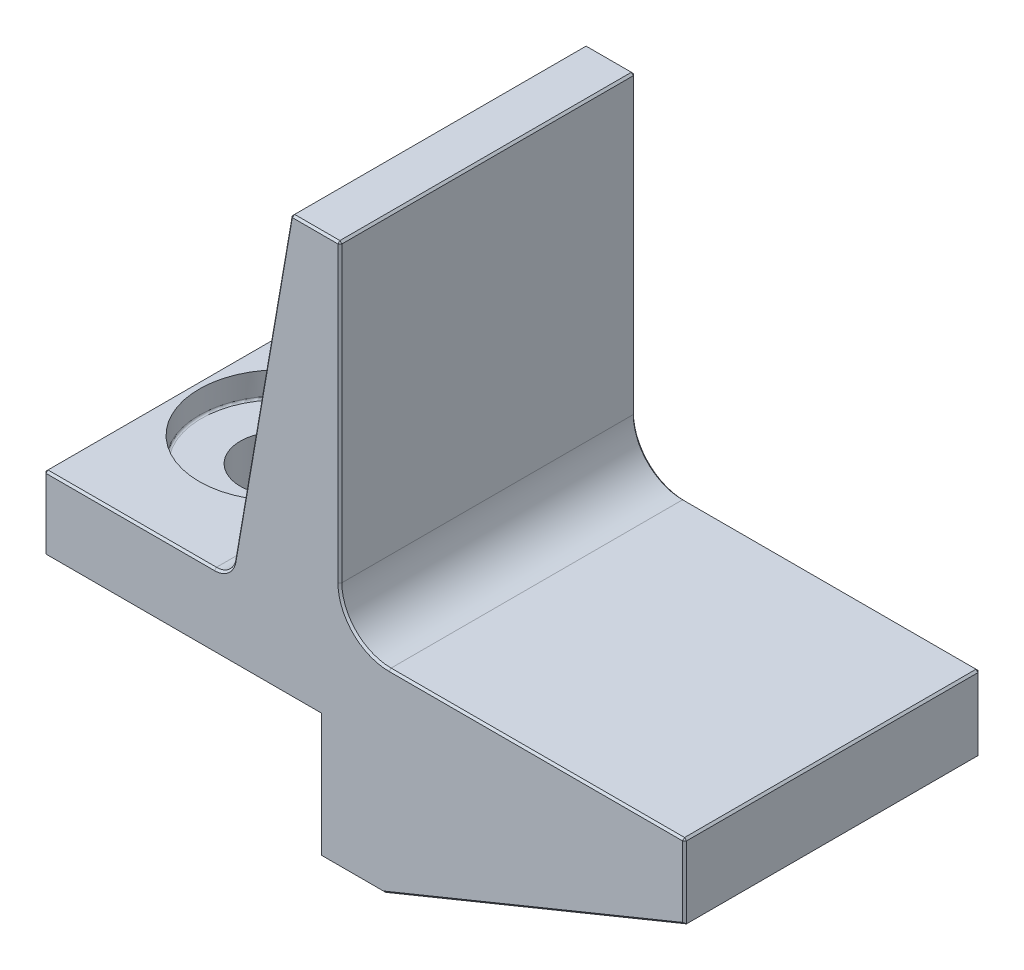
SolidWorks part; units mm, degrees
material "7075-T6 (SN)"
ref_plane "Front Plane" through (0, 0, 0) normal (0, 0, 1) x (1, 0, 0)
ref_plane "Top Plane" through (0, 0, 0) normal (0, 1, 0) x (1, 0, 0)
ref_plane "Right Plane" through (0, 0, 0) normal (1, 0, 0) x (0, 0, -1)
sketch "Sketch1" plane through (0, 0, 0) normal (0, 0, 1) x (1, 0, 0)
  line L0 (0, 0) -> (44.45, 0)
  line L1 (44.45, 0) -> (44.45, -9.525)
  line L2 (-2.6008, -9.525) -> (-38.1608, -9.525)
  line L3 (-38.1608, -9.525) -> (-38.1608, 0)
  line L4 (-38.1608, 0) -> (-14.0308, 0)
  line L5 (-14.0308, 0) -> (-6.35, 44.45)
  line L6 (-6.35, 44.45) -> (0, 44.45)
  line L7 (0, 44.45) -> (0, 0)
  line L8 (-2.6008, -9.525) -> (-2.6008, -25.4)
  line L9 (-2.6008, -25.4) -> (5.6542, -25.4)
  line L10 (5.6542, -25.4) -> (44.45, -9.525)
  dimension "D1" = 44.45
  dimension "D2" = 44.45
  dimension "D3" = 9.525
  dimension "D4" = 38.1608
  dimension "D5" = 6.35
  dimension "D6" = 24.13
  dimension "D7" = 35.56
  dimension "D8" = 9.525
  dimension "D9" = 15.875
  dimension "D10" = 8.255
extrude "Boss-Extrude1" add sketch "Sketch1" along normal blind 38.1
hole_wizard "CBORE for 3/8 Binding Head Machine Screw1" positions "Sketch6" profile "Sketch3" counterbore size "3/8" standard "ANSI Inch" end condition through all
sketch "Sketch6" plane through (0, 0, 0) normal (0, 1, 0) x (1, 0, 0)
  line L1 (-38.1608, -38.1) -> (-38.1608, 0) construction
  point P0 (-26.8578, -19.05)
  point P8 (-38.1608, -19.05)
  dimension "D1" = 11.303
sketch "Sketch3" plane through (-26.8578, 0, 19.05) normal (1, 0, 0) x (0, 0, 1)
  line L0 (0, 0) -> (0, 25.4)
  line L1 (0, 25.4) -> (5.0419, 25.4)
  line L3 (5.0419, 25.4) -> (5.0419, 3.175)
  line L4 (10.3378, 3.175) -> (5.0419, 3.175)
  line L5 (10.3378, 3.175) -> (10.3378, 0)
  line L7 (10.3378, 0) -> (0, 0)
  line L11 (0, 0) -> (0, 107.95) construction
  dimension "Thru Hole Dia." = 10.0838
  dimension "Thru Hole Depth" = 25.4
  dimension "C'Bore Depth" = 3.175
fillet "Fillet1" radius 2.54 1 edges at (-14.0308, 0, 19.05)
fillet "Fillet2" radius 6.35 1 edges at (0, 0, 19.05)
chamfer "Chamfer1" distance 0.254 angle 45 31 edges at (-6.35, 44.45, 19.05) (-3.175, 44.45, 0) (-10.0083, 23.2788, 0) (-14.5335, 0.597, 0) (-27.1652, 0, 0) (-38.1608, -4.7625, 0) (-20.3808, -9.525, 0) (44.45, -4.7625, 0) (25.4, 0, 0) (1.8599, 1.8599, 0) (0, 25.4, 0) (44.45, -4.7625, 38.1) (-20.3808, -9.525, 38.1) (-38.1608, -9.525, 19.05) (-38.1608, -4.7625, 38.1) (-38.1608, 0, 19.05) (-27.1652, 0, 38.1) (-14.5335, 0.597, 38.1) (-10.0083, 23.2788, 38.1) (-3.175, 44.45, 38.1) (0, 44.45, 19.05) (0, 25.4, 38.1) (1.8599, 1.8599, 38.1) (25.4, 0, 38.1) (44.45, 0, 19.05) (-2.6008, -17.4625, 0) (1.5267, -25.4, 0) (25.0521, -17.4625, 0) (25.0521, -17.4625, 38.1) (1.5267, -25.4, 38.1) (-2.6008, -17.4625, 38.1) first distance on face at (-3.175, 44.45, 19.05) first distance on face at (-10.0083, 23.2788, 19.05) first distance on face at (-14.7258, 0.8254, 19.05) first distance on face at (-26.8578, 0, 29.3878) first distance on face at (-38.1608, -4.7625, 19.05) first distance on face at (-31.8997, -9.525, 19.05) first distance on face at (44.45, -4.7625, 19.05) first distance on face at (-1.3643, 1.247, 0) first distance on face at (2.5174, 2.5174, 19.05) first distance on face at (0, 25.4, 19.05) first distance on face at (-1.3643, 1.247, 38.1) first distance on face at (-2.6008, -17.4625, 19.05) first distance on face at (1.5267, -25.4, 19.05) first distance on face at (25.0521, -17.4625, 19.05)
fillet "Fillet3" radius 0.254 1 edges at (-26.8578, -3.175, 29.3878)
chamfer "Chamfer2" distance 0.254 angle 45 1 edges at (-31.8997, -9.525, 19.05)
